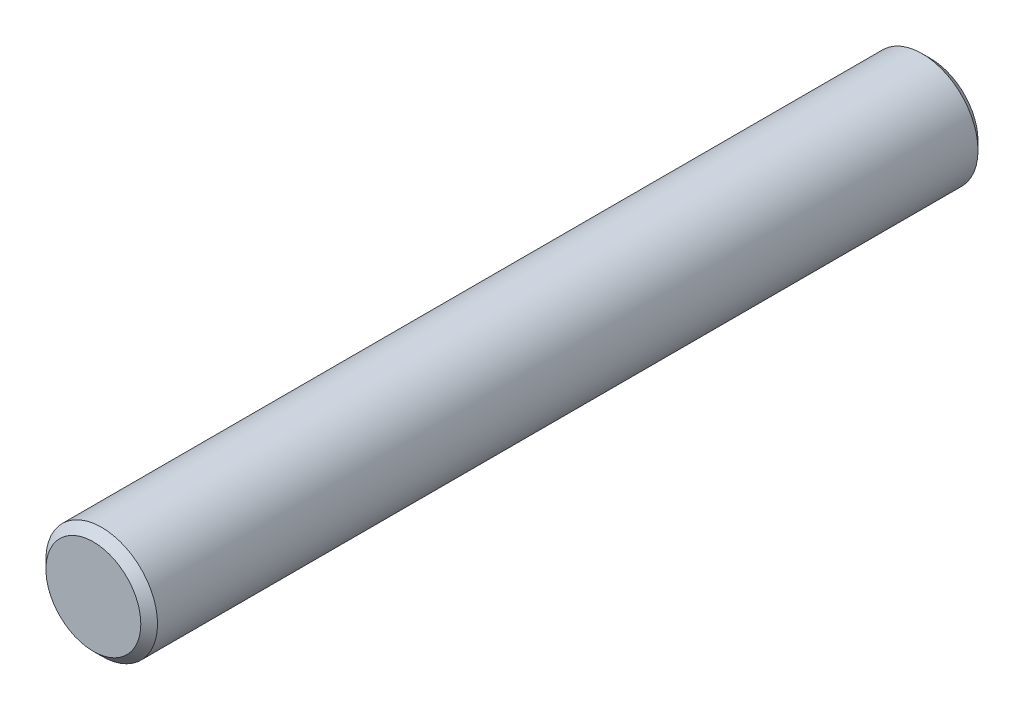
SolidWorks part; units mm, degrees
ref_plane "Front Plane" through (0, 0, 0) normal (0, 0, 1) x (1, 0, 0)
ref_plane "Top Plane" through (0, 0, 0) normal (0, 1, 0) x (1, 0, 0)
ref_plane "Right Plane" through (0, 0, 0) normal (1, 0, 0) x (0, 0, -1)
sketch "Sketch1" plane through (0, 0, 0) normal (0, 0, 1) x (1, 0, 0)
  line L0 (-4, 0) -> (4, 0) construction
  line L5 (0, 4) -> (0, -4) construction
  circle A1 centre (0, 0) radius 4
  point P7 (-4, 0)
  point P8 (4, 0)
  point P12 (0, -4)
  point P13 (0, 4)
  dimension "Diameter" = 8
sketch "Sketch2" plane through (0, 0, 0) normal (1, 0, 0) x (0, 0, -1)
  line L10 (-30, 0) -> (30, 0) construction
  line L11 (30, -4) -> (-30, -4)
  line L12 (30, -4) -> (30, 4)
  line L13 (30, 4) -> (-30, 4)
  line L14 (-30, -4) -> (-30, 4)
  line L15 (-20, 4) -> (-20, -4)
  line L16 (20, 4) -> (20, -4)
  line L17 (-20, 0) -> (20, 0) construction
  line L18 (-29.4, 4) -> (-30, 3.4) construction
  point P0 (0, 0)
  point P4 (0, 0)
  point P28 (0, 0)
  dimension "Chamfer Typ," = 45
  dimension "Length" = 60
  dimension "Chamfer Length" = 0.6
  dimension "D1" = 10
sketch "Sketch3" plane through (0, 0, 0) normal (0, 0, 1) x (1, 0, 0)
  circle A0 centre (0, 0) radius 4 construction
  circle A1 centre (0, 0) radius 4
extrude "Boss-Extrude1" add sketch "Sketch3" along normal up to vertex (-30 mm away) and the other way up to vertex (30 mm away) up to point (0, 4, -30) other way up to point (0, 4, -30)
chamfer "Chamfer1" distance 0.6 angle 45 2 edges at (4, 0, -30) (4, 0, 30)
ref_axis "Axis1" through (0, 0, 29.4) along (0, 0, -1)
equation "\"D1@Chamfer1\"=\"Chamfer Length@Sketch2\""
equation "\"D2@Chamfer1\"=\"Chamfer Typ,@Sketch2\""
equation "\"Chamfer Length@Sketch2\" = \"Diameter@Sketch1\" * .075"
